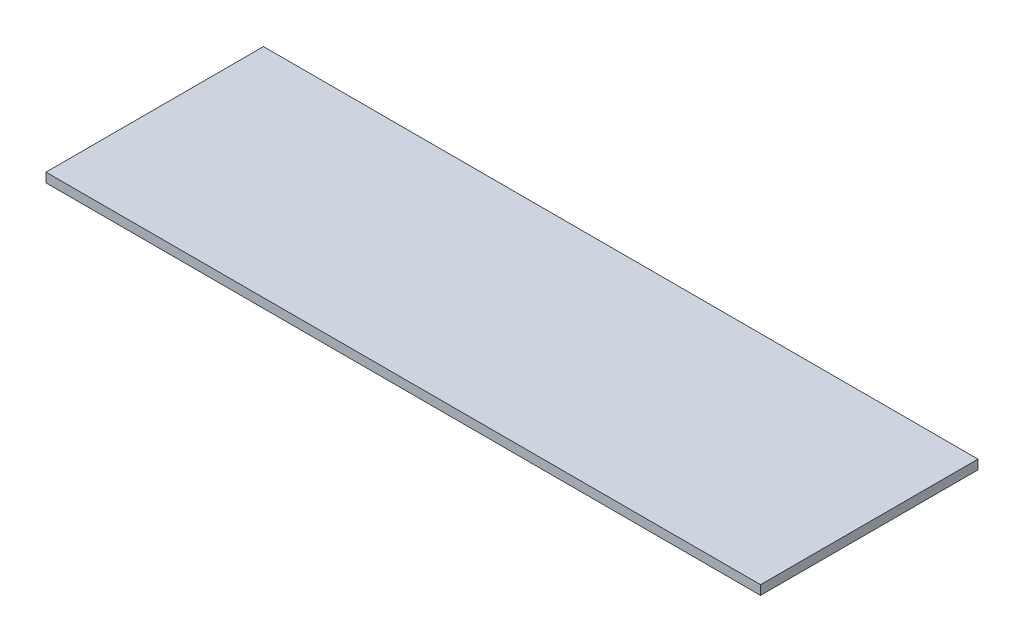
SolidWorks part; units mm, degrees
ref_plane "Front Plane" through (0, 0, 0) normal (0, 0, 1) x (1, 0, 0)
ref_plane "Top Plane" through (0, 0, 0) normal (0, 1, 0) x (1, 0, 0)
ref_plane "Right Plane" through (0, 0, 0) normal (1, 0, 0) x (0, 0, -1)
sketch "Sketch1" plane through (0, 0, 0) normal (0, 1, 0) x (1, 0, 0)
  line L1 (-115, -35) -> (115, -35)
  line L2 (-115, -35) -> (-115, 35)
  line L3 (-115, 35) -> (115, 35)
  line L4 (115, -35) -> (115, 35)
  line L5 (-115, -35) -> (115, 35) construction
  line L6 (-115, 35) -> (115, -35) construction
  point P0 (0, 0)
  dimension "D1" = 230
  dimension "D2" = 70
extrude "Boss-Extrude1" add sketch "Sketch1" along normal blind 3
